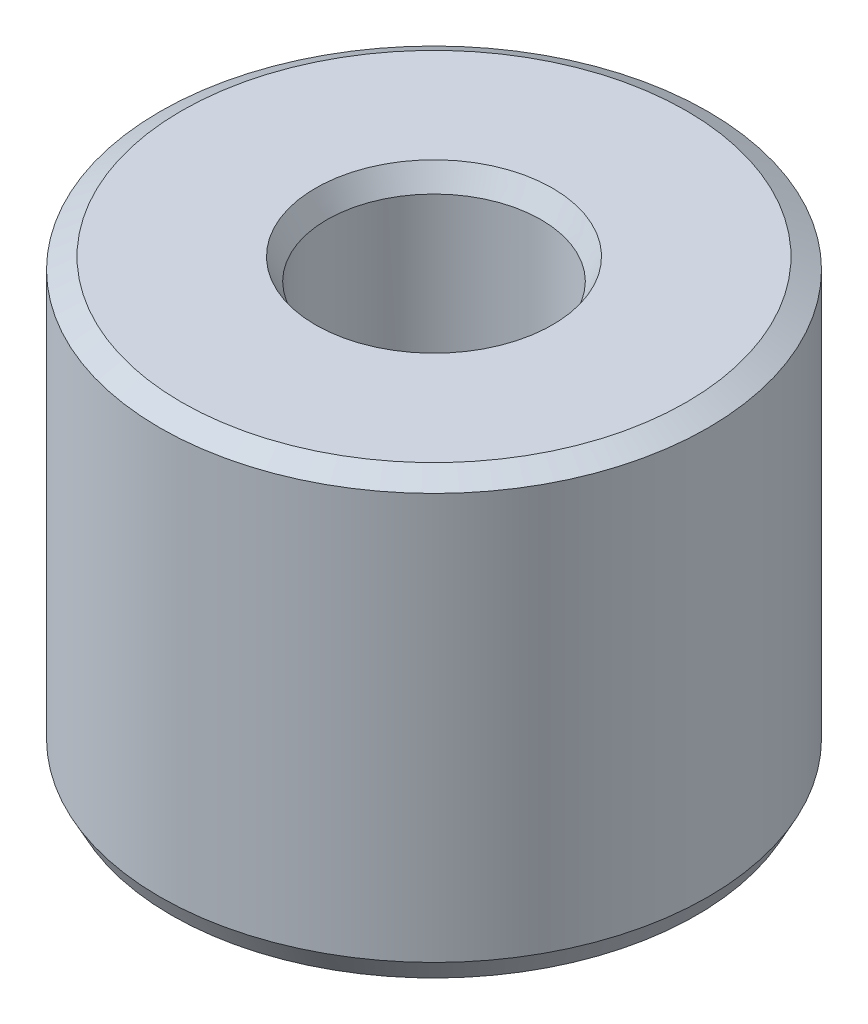
SolidWorks part; units mm, degrees
ref_plane "Front Plane" through (0, 0, 0) normal (0, 0, 1) x (1, 0, 0)
ref_plane "Top Plane" through (0, 0, 0) normal (0, 1, 0) x (1, 0, 0)
ref_plane "Right Plane" through (0, 0, 0) normal (1, 0, 0) x (0, 0, -1)
sketch "Sketch1" plane through (0, 0, 0) normal (0, 1, 0) x (1, 0, 0)
  circle A0 centre (0, 0) radius 45
  dimension "SLEEVE_OD" = 90
extrude "Boss-Extrude1" add sketch "Sketch1" along normal blind 72.1281
sketch "Sketch2" plane through (0, 0, 0) normal (0, 1, 0) x (1, 0, 0)
  circle A0 centre (0, 0) radius 17.5771
  dimension "BORE_D" = 35.1542
extrude "Cut-Extrude1" cut sketch "Sketch2" along normal through all
chamfer "Chamfer1" distance 1.8807 angle 62.027 4 edges at (0, 72.1281, 17.5771) (0, 0, 17.5771) (0, 0, 45) (0, 72.1281, 45) first distance on face at (0, 72.1281, 17.5771) first distance on face at (0, 0, 17.5771) first distance on face at (0, 72.1281, 45)
